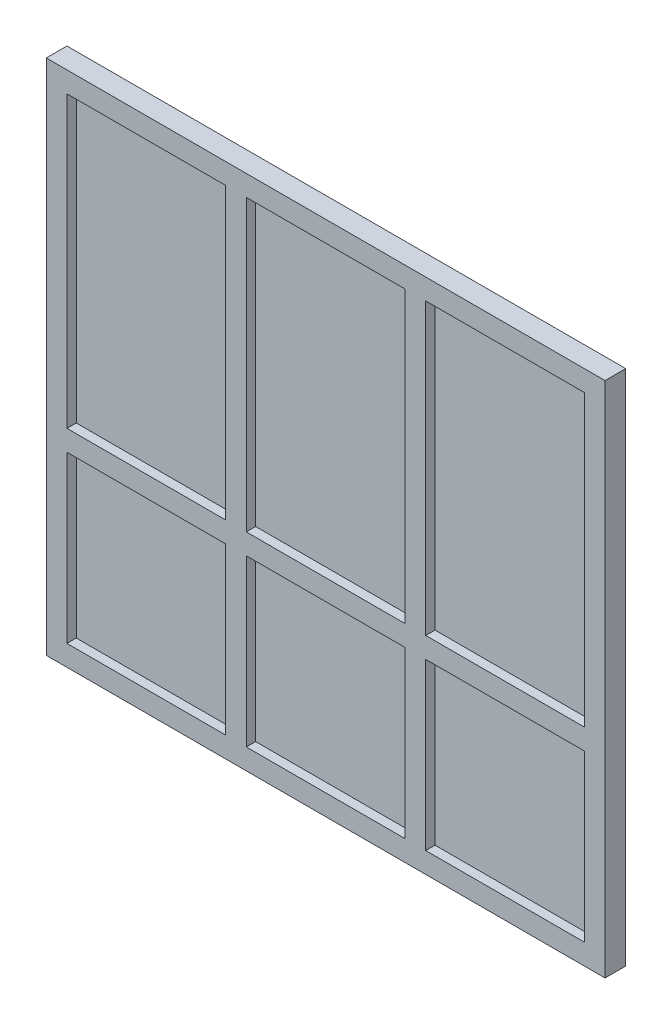
SolidWorks part; units mm, degrees
ref_plane "Спереди" through (0, 0, 0) normal (0, 0, 1) x (1, 0, 0)
ref_plane "Сверху" through (0, 0, 0) normal (0, 1, 0) x (1, 0, 0)
ref_plane "Справа" through (0, 0, 0) normal (1, 0, 0) x (0, 0, -1)
other "Configuration Table"
sketch "Эскиз1" plane through (0, 0, 0) normal (0, 0, 1) x (1, 0, 0)
  line L0 (-1215, 2400) -> (-1215, 1000)
  line L1 (1385, 0) -> (-1315, 0)
  line L2 (1385, 0) -> (1385, 2500)
  line L3 (1385, 2500) -> (-1315, 2500)
  line L4 (-1315, 0) -> (-1315, 2500)
  line L5 (-1215, 1000) -> (-448.3333, 1000)
  line L6 (-448.3333, 1000) -> (-448.3333, 2400)
  line L7 (-1215, 2400) -> (-448.3333, 2400)
  line L9 (-1215, 100) -> (-448.3333, 100)
  line L11 (-348.3333, 2400) -> (418.3333, 2400)
  line L13 (-348.3333, 100) -> (418.3333, 100)
  line L15 (518.3333, 2400) -> (1285, 2400)
  line L17 (518.3333, 100) -> (1285, 100)
  line L19 (-1215, 100) -> (-1215, 900)
  line L20 (-1215, 900) -> (-448.3333, 900)
  line L21 (-448.3333, 900) -> (-448.3333, 100)
  line L22 (-348.3333, 100) -> (-348.3333, 900)
  line L23 (-348.3333, 900) -> (418.3333, 900)
  line L24 (418.3333, 900) -> (418.3333, 100)
  line L25 (518.3333, 100) -> (518.3333, 900)
  line L26 (518.3333, 900) -> (1285, 900)
  line L27 (1285, 900) -> (1285, 100)
  line L28 (-348.3333, 2400) -> (-348.3333, 1000)
  line L29 (-348.3333, 1000) -> (418.3333, 1000)
  line L30 (418.3333, 1000) -> (418.3333, 2400)
  line L31 (518.3333, 2400) -> (518.3333, 1000)
  line L32 (518.3333, 1000) -> (1285, 1000)
  line L33 (1285, 1000) -> (1285, 2400)
  line L34 (-448.3333, 2400) -> (-348.3333, 2400) construction
  line L35 (418.3333, 2400) -> (518.3333, 2400) construction
  line L36 (-448.3333, 900) -> (-348.3333, 900) construction
  line L37 (1285, 2400) -> (1385, 2400) construction
  line L38 (418.3333, 900) -> (518.3333, 900) construction
  line L39 (1285, 900) -> (1285, 1000) construction
  line L40 (518.3333, 900) -> (518.3333, 1000) construction
  line L41 (418.3333, 900) -> (418.3333, 1000) construction
  line L42 (418.3333, 1000) -> (518.3333, 1000) construction
  line L43 (-448.3333, 1000) -> (-348.3333, 1000) construction
  line L44 (-348.3333, 1000) -> (-348.3333, 900) construction
  line L45 (-448.3333, 900) -> (-448.3333, 1000) construction
  line L46 (-1215, 900) -> (-1215, 1000) construction
  line L47 (-448.3333, 100) -> (-348.3333, 100) construction
  line L48 (418.3333, 100) -> (518.3333, 100) construction
  line L49 (-1215, 2400) -> (-1315, 2400) construction
  line L50 (-1315, 2400) -> (-1215, 2400) construction
  line L51 (-1215, 2400) -> (-1215, 2500) construction
  line L52 (-1215, 100) -> (-1215, 0) construction
  point P0 (35, 0)
  dimension "D3" = 1400
  dimension "D4" = 100
extrude "Бобышка-Вытянуть1" add sketch "Эскиз1" along normal blind 100
ref_plane "Плоскость1" through (0, 0, 50) normal (0, 0, -1) x (-1, 0, 0)
sketch "Эскиз2" plane through (0, 0, 50) normal (0, 0, -1) x (-1, 0, 0)
  line L1 (-1285, 2400) -> (1215, 2400)
  line L2 (-1285, 2400) -> (-1285, 100)
  line L3 (-1285, 100) -> (1215, 100)
  line L4 (1215, 2400) -> (1215, 100)
extrude "Бобышка-Вытянуть2" add sketch "Эскиз2" along normal mid plane 10 separate body
